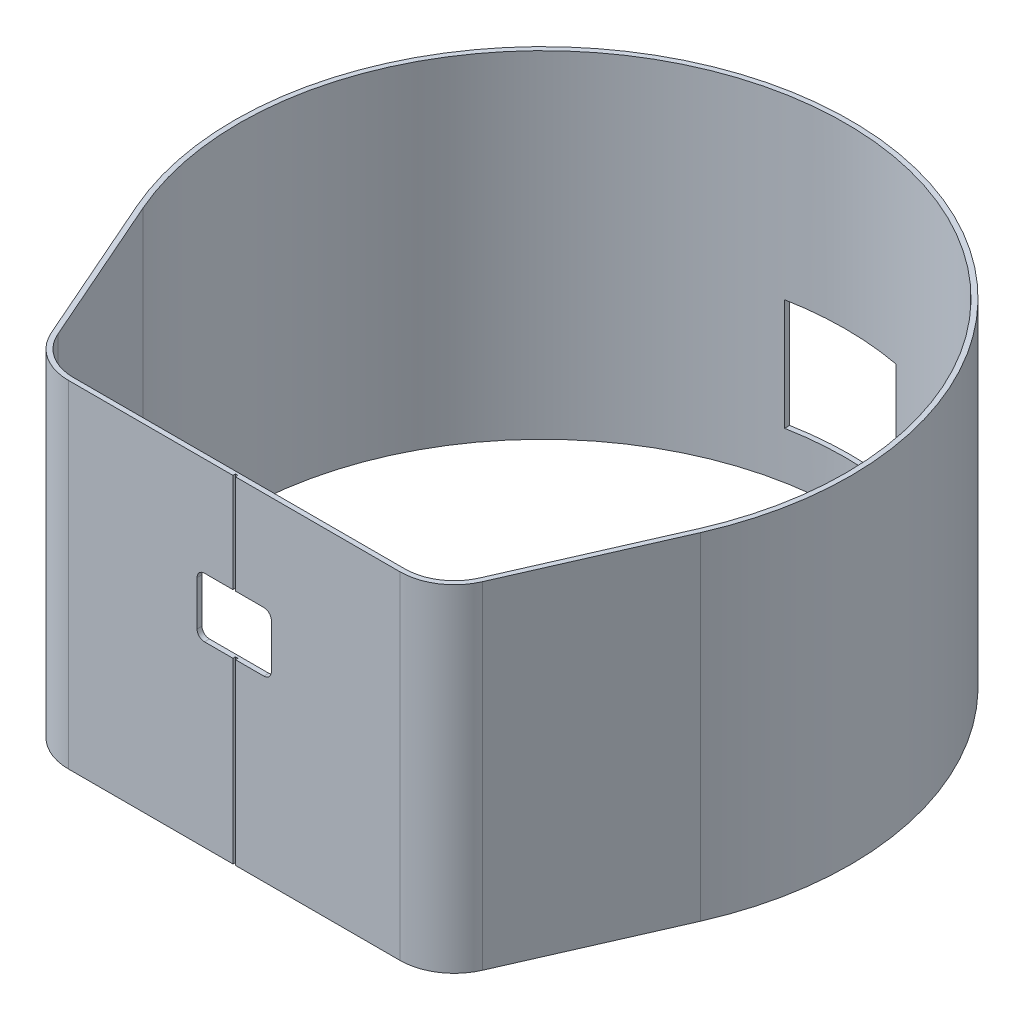
SolidWorks part; units mm, degrees
ref_plane "Front Plane" through (0, 0, 0) normal (0, 0, 1) x (1, 0, 0)
ref_plane "Top Plane" through (0, 0, 0) normal (0, 1, 0) x (1, 0, 0)
ref_plane "Right Plane" through (0, 0, 0) normal (1, 0, 0) x (0, 0, -1)
sketch "Sketch1" plane through (0, 0, 0) normal (0, 1, 0) x (1, 0, 0)
  line L0 (-33.4694, -61.25) -> (33.4694, -61.25)
  line L1 (42.6256, -55.2704) -> (56.0818, -24.6252)
  line L2 (0, 0) -> (0, -61.25) construction
  line L3 (0, 0) -> (56.0818, -24.6252) construction
  line L4 (-42.6256, -55.2704) -> (-56.0818, -24.6252)
  line L5 (43.5412, -55.6725) -> (56.9974, -25.0272)
  line L6 (-33.4694, -62.25) -> (33.4694, -62.25)
  line L7 (-43.5412, -55.6725) -> (-56.9974, -25.0272)
  circle A0 centre (0, 0) radius 61.25
  arc A1 (33.4694, -61.25) -> (42.6256, -55.2704) centre (33.4694, -51.25) ccw
  arc A2 (-42.6256, -55.2704) -> (-33.4694, -61.25) centre (-33.4694, -51.25) ccw
  arc A3 (33.4694, -62.25) -> (43.5412, -55.6725) centre (33.4694, -51.25) ccw
  arc A4 (-43.5412, -55.6725) -> (-33.4694, -62.25) centre (-33.4694, -51.25) ccw
  arc A6 (56.9974, -25.0272) -> (-56.9974, -25.0272) centre (0, 0) ccw
  point P10 (40, -61.25)
  point P13 (-40, -61.25)
  dimension "D1" = 122.5
  dimension "D4" = 10
  dimension "D2" = 40
  dimension "D3" = 90
  dimension "D5" = 1
extrude "Boss-Extrude1" add sketch "Sketch1" along normal blind 90 contours L5 A6 L7 A4 L6 A3 A2 L4 A0 L1 A1 L0 region at (39.3878, 0, 60.3126)
sketch "Sketch2" plane through (0, 0, 0) normal (1, 0, 0) x (0, 0, -1)
  line L0 (0, 0) -> (0, 108.1755) construction
  line L1 (-25.0272, 0) -> (62.25, 0) construction
  line L2 (-21.9317, 22) -> (21.9317, 22)
  line L4 (0, 22) -> (62.25, 22)
  line L5 (0, 22) -> (0, 0)
  line L6 (0, 0) -> (62.25, 0)
  line L7 (62.25, 22) -> (62.25, 0)
  line L8 (0, 22) -> (-62.4653, 22)
  line L9 (0, 22) -> (0, 0)
  line L10 (0, 0) -> (-62.4653, 0)
  line L11 (-62.4653, 22) -> (-62.4653, 0)
  circle A0 centre (0, 10) radius 25
  dimension "D1" = 50
  dimension "D2" = 10
  dimension "D3" = 22
extrude "Cut-Extrude1" cut sketch "Sketch2" against normal through all and the other way through all contours L2 A0 | L6 A0 L2 L5 | A0 L6 L7 L4 | A0 L8 L11 L10 | L2 A0 L10 L5 region at (0, 11.0449, 43.2971) region at (0, 10.9288, 12.0863) region at (0, 10.9288, -12.0863) region at (0, 11.0451, -43.1894)
sketch "Sketch4" plane through (0, 0, 0) normal (0, 0, 1) x (1, 0, 0)
  line L0 (0, 0) -> (0, 75.2026) construction
  line L1 (-62.25, 22) -> (62.25, 22) construction
  line L2 (11.25, 31.5) -> (-11.25, 31.5)
  line L3 (11.25, 31.5) -> (11.25, 54)
  line L4 (11.25, 54) -> (-11.25, 54)
  line L5 (-11.25, 31.5) -> (-11.25, 54)
  line L6 (11.25, 31.5) -> (-11.25, 54) construction
  line L7 (11.25, 54) -> (-11.25, 31.5) construction
  point P3 (0, 42.75)
  dimension "D1" = 32
  dimension "D2" = 22.5
  dimension "D3" = 22.5
extrude "Cut-Extrude3" cut sketch "Sketch4" against normal through all
sketch "Sketch5" plane through (0, 0, 62.25) normal (0, 0, 1) x (1, 0, 0)
  line L0 (0, 0) -> (0, 79.7879) construction
  line L2 (-6, 58) -> (6, 58)
  line L3 (-7.5, 59.5) -> (-7.5, 68.5)
  line L4 (-6, 70) -> (6, 70)
  line L5 (7.5, 59.5) -> (7.5, 68.5)
  line L6 (-7.5, 58) -> (7.5, 70) construction
  line L7 (-7.5, 70) -> (7.5, 58) construction
  line L8 (33.4694, 22) -> (-33.4694, 22) construction
  arc A0 (7.5, 68.5) -> (6, 70) centre (6, 68.5) ccw
  arc A1 (6, 58) -> (7.5, 59.5) centre (6, 59.5) ccw
  arc A2 (-7.5, 59.5) -> (-6, 58) centre (-6, 59.5) ccw
  arc A3 (-7.5, 68.5) -> (-6, 70) centre (-6, 68.5) cw
  point P3 (0, 64)
  dimension "D4" = 1.5
  dimension "D2" = 15
  dimension "D3" = 12
  dimension "D5" = 42
extrude "Cut-Extrude4" cut sketch "Sketch5" against normal blind 3
sketch "Sketch6" plane through (0, 0, 62.25) normal (0, 0, 1) x (1, 0, 0)
  line L0 (0, 90) -> (0, 22) construction
  line L1 (-33.4694, 90) -> (33.4694, 90) construction
  line L2 (33.4694, 22) -> (-33.4694, 22) construction
  line L3 (-0.25, 90) -> (-0.25, 22)
  line L4 (0.25, 90) -> (0.25, 22)
  line L5 (-0.25, 22) -> (0.25, 22)
  line L6 (-0.25, 90) -> (0.25, 90)
  dimension "D1" = 0.25
extrude "Cut-Extrude5" cut sketch "Sketch6" against normal blind 0.5
